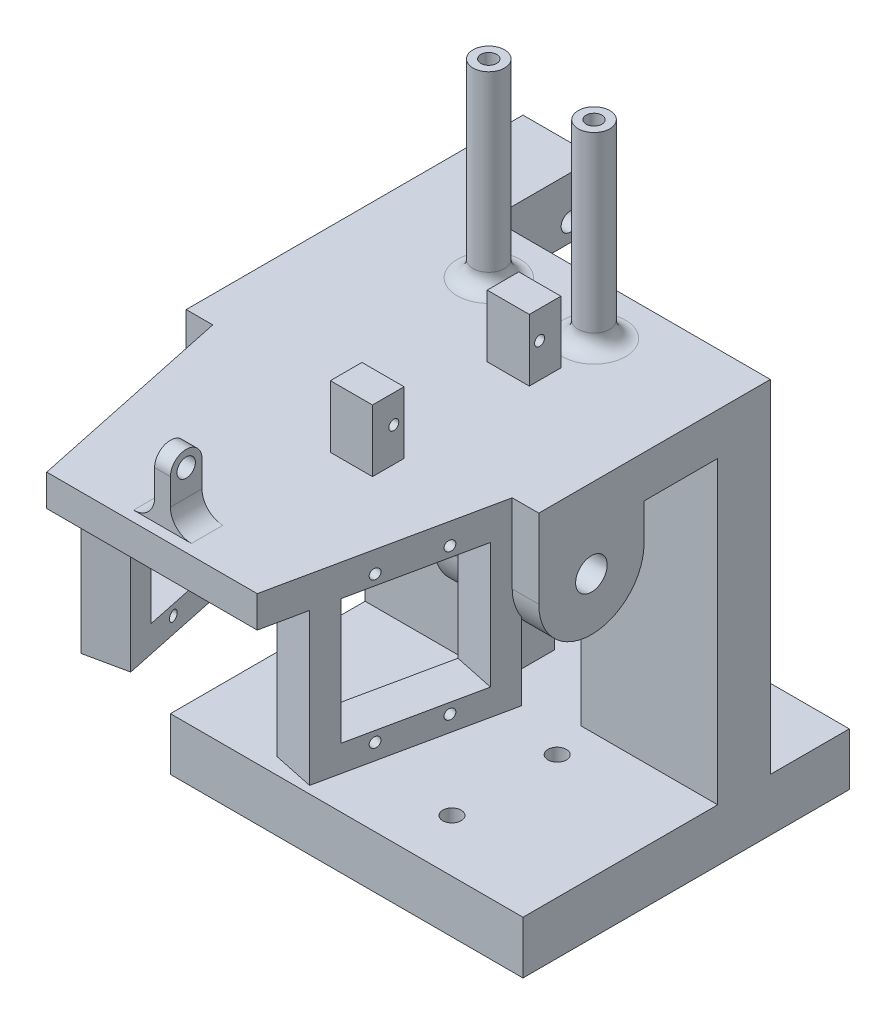
SolidWorks part; units mm, degrees
ref_plane "前视基准面" through (0, 0, 0) normal (0, 0, 1) x (1, 0, 0)
ref_plane "上视基准面" through (0, 0, 0) normal (0, 1, 0) x (1, 0, 0)
ref_plane "右视基准面" through (0, 0, 0) normal (1, 0, 0) x (0, 0, -1)
sketch "草图1" plane through (0, 0, 0) normal (0, 1, 0) x (1, 0, 0)
  line L1 (-33.5, 31) -> (33.5, 31)
  line L2 (-33.5, 31) -> (-33.5, -31)
  line L3 (-33.5, -31) -> (33.5, -31)
  line L4 (33.5, 31) -> (33.5, -31)
  line L5 (-33.5, 31) -> (33.5, -31) construction
  line L6 (-33.5, -31) -> (33.5, 31) construction
  point P0 (0, 0)
  dimension "D1" = 62
  dimension "D2" = 67
extrude "凸台-拉伸1" add sketch "草图1" along normal blind 10
sketch "草图3" plane through (0, 10, 0) normal (0, 1, 0) x (1, 0, 0)
  line L0 (-33.5, 31) -> (-33.5, -31) construction
  line L1 (-33.5, 36) -> (-19.5, 36)
  line L2 (-33.5, 36) -> (-33.5, 16)
  line L3 (-33.5, 16) -> (-19.5, 16)
  line L4 (-19.5, 36) -> (-19.5, 16)
  line L5 (33.5, 31) -> (-33.5, 31) construction
  dimension "D1" = 20
  dimension "D2" = 5
  dimension "D3" = 19.5
extrude "凸台-拉伸2" add sketch "草图3" along normal blind 12.5
sketch "草图4" plane through (-33.5, 0, 0) normal (-1, 0, 0) x (0, 0, 1)
  line L1 (-16, 10) -> (-6, 10)
  line L2 (-16, 10) -> (-16, 75)
  line L3 (-16, 75) -> (-6, 75)
  line L4 (-6, 10) -> (-6, 75)
  dimension "D1" = 10
  dimension "D2" = 65
extrude "凸台-拉伸3" add sketch "草图4" against normal blind 67
sketch "草图5" plane through (0, 75, 0) normal (0, 1, 0) x (1, 0, 0)
  line L0 (33.5, -31) -> (33.5, 6) construction
  line L1 (-33.5, 16) -> (33.5, 16)
  line L2 (-33.5, 16) -> (-33.5, -28)
  line L3 (-33.5, -28) -> (33.5, -28)
  line L4 (33.5, 16) -> (33.5, -28)
  dimension "D1" = 44
extrude "凸台-拉伸4" add sketch "草图5" against normal blind 8
sketch "草图6" plane through (33.5, 0, 0) normal (1, 0, 0) x (0, 0, -1)
  line L0 (6, 10) -> (6, 67) construction
  line L1 (-28, 75) -> (16, 75) construction
  line L2 (-28, 60) -> (-28, 67)
  line L3 (-28, 67) -> (6, 67) construction
  line L5 (-28, 67) -> (-8, 67)
  line L6 (-8, 67) -> (-8, 60)
  arc A0 (-28, 60) -> (-8, 60) centre (-18, 60) ccw
  dimension "D1" = 24
  dimension "D2" = 15
  dimension "D3" = 20
extrude "凸台-拉伸5" add sketch "草图6" against normal blind 20
sketch "草图7" plane through (33.5, 0, 0) normal (1, 0, 0) x (0, 0, -1)
  line L0 (-28, 60) -> (-28, 70.0002)
  line L1 (-28, 60) -> (-28, 75) construction
  line L2 (-28, 70.0002) -> (-8, 70.0002)
  line L3 (-8, 70.0002) -> (-8, 60)
  arc A0 (-28, 60) -> (-8, 60) centre (-18, 60) ccw construction
  arc A1 (-28, 60) -> (-8, 60) centre (-18, 60) ccw
extrude "切除-拉伸1" cut sketch "草图7" against normal blind 8 from offset 6 offset against normal yes
sketch "草图8" plane through (0, 75, 0) normal (0, 1, 0) x (1, 0, 0)
  line L0 (0, -68) -> (20, -68)
  line L2 (20, -68) -> (28.4525, -28)
  line L3 (28.4525, -28) -> (0, -28)
  line L4 (0, -28) -> (0, -68)
  line L5 (-33.5, -28) -> (33.5, -28) construction
  dimension "D1" = 20
  dimension "D2" = 40
extrude "凸台-拉伸6" add sketch "草图8" against normal blind 6
sketch "草图9" plane through (33.5, 0, 0) normal (1, 0, 0) x (0, 0, -1)
  circle A0 centre (-18, 60) radius 3
  dimension "D1" = 6
extrude "切除-拉伸2" cut sketch "草图9" against normal blind 23
sketch "草图10" plane through (32.9001, 0, 6.9522) normal (0.9784, 0, 0.2067) x (0.2067, 0, -0.9784)
  line L1 (-49, 75) -> (-20, 75)
  line L4 (-20, 75) -> (-20, 40.2)
  line L5 (-20, 40.2) -> (-48, 40.2)
  line L9 (-49, 45.2) -> (-25, 45.2)
  line L10 (-25, 45.2) -> (-25, 69)
  line L11 (-25, 69) -> (-49, 69)
  line L12 (-62.3959, 75) -> (-21.5126, 75) construction
  line L14 (-49, 75) -> (-54, 75)
  line L15 (-62.3959, 75) -> (-21.5126, 75) construction
  line L16 (-49, 69) -> (-49, 45.2)
  line L17 (-48, 40.2) -> (-54, 40.2)
  line L18 (-54, 75) -> (-54, 40.2)
  dimension "D1" = 5
  dimension "D2" = 5
  dimension "D3" = 29
  dimension "D4" = 20
  dimension "D5" = 24
  dimension "D6" = 28
  dimension "D7" = 5
  dimension "D8" = 6
  dimension "D9" = 23.8
extrude "凸台-拉伸7" add sketch "草图10" against normal blind 8
sketch "草图12" plane through (0, 75, 0) normal (0, 1, 0) x (1, 0, 0)
  line L1 (-33.5, 36) -> (-19.5, 36)
  line L2 (-33.5, 36) -> (-33.5, 16)
  line L3 (-33.5, 16) -> (-19.5, 16)
  line L4 (-19.5, 36) -> (-19.5, 16)
extrude "凸台-拉伸8" add sketch "草图12" against normal blind 11.5
sketch "草图13" plane through (25.0729, 0, 5.2982) normal (-0.9784, 0, -0.2067) x (-0.2067, 0, 0.9784)
  line L0 (62.3959, 69) -> (54, 69) construction
  line L7 (25, 69) -> (25, 45.2) construction
  line L8 (25, 45.2) -> (49, 45.2) construction
  circle A0 centre (43.5, 70.95) radius 0.95
  circle A1 centre (31.5, 70.95) radius 0.95
  circle A2 centre (31.5, 43.25) radius 0.95
  circle A3 centre (43.5, 43.25) radius 0.95
  dimension "D2" = 6.5
  dimension "D3" = 1.95
  dimension "D4" = 1.95
  dimension "D5" = 12
  dimension "D6" = 1.9
  dimension "D7" = 1.9
  dimension "D13" = 1.9
  dimension "D14" = 1.9
extrude "切除-拉伸4" cut sketch "草图13" against normal up to surface (8 mm away) up to face at (24.7288, 60.3828, 45.6217)
sketch "草图14" plane through (0, 75, 0) normal (0, 1, 0) x (1, 0, 0)
  line L0 (33.5, 6) -> (-33.5, 6) construction
  line L1 (3.7, -2) -> (11.7, -2)
  line L2 (3.7, -2) -> (3.7, -8)
  line L3 (3.7, -8) -> (11.7, -8)
  line L4 (11.7, -2) -> (11.7, -8)
  line L5 (11.7, -31.8) -> (11.7, -37.8)
  line L6 (3.7, -37.8) -> (11.7, -37.8)
  line L7 (3.7, -31.8) -> (3.7, -37.8)
  line L8 (3.7, -31.8) -> (11.7, -31.8)
  dimension "D1" = 11.7
  dimension "D2" = 3.7
  dimension "D3" = 6
  dimension "D4" = 14
  dimension "D5" = 6
  dimension "D6" = 8
  dimension "D7" = 23.8
extrude "凸台-拉伸9" add sketch "草图14" along normal blind 11.8
sketch "草图15" plane through (3.7, 0, 0) normal (-1, 0, 0) x (0, 0, 1)
  line L0 (8, 86.8) -> (8, 75) construction
  line L1 (28, 75) -> (-36, 75) construction
  line L2 (31.8, 75) -> (37.8, 75) construction
  line L3 (31.8, 86.8) -> (31.8, 75) construction
  circle A0 centre (33.75, 81.5) radius 0.95
  circle A1 centre (6.05, 81.5) radius 0.95
  dimension "D1" = 1.95
  dimension "D2" = 1.95
  dimension "D3" = 1.9
  dimension "D4" = 1.9
  dimension "D5" = 6.5
  dimension "D6" = 6.5
extrude "切除-拉伸5" cut sketch "草图15" against normal blind 11.8
sketch "草图16" plane through (0, 75, 0) normal (0, 1, 0) x (1, 0, 0)
  line L1 (-1.5, -60) -> (1.5, -60)
  line L2 (-1.5, -60) -> (-1.5, -66)
  line L3 (-1.5, -66) -> (1.5, -66)
  line L4 (1.5, -60) -> (1.5, -66)
  point P4 (0, -66)
  dimension "D2" = 6
  dimension "D3" = 3
  dimension "D4" = 60
extrude "凸台-拉伸10" add sketch "草图16" along normal blind 12
fillet "圆角1" 2 edges at (0, 87, 66) (0, 87, 60) type full round first side face at (0, 79.8, 66) second side face at (0, 79.8, 60) middle face at (0, 87, 63)
sketch "草图17" plane through (-1.5, 0, 0) normal (-1, 0, 0) x (0, 0, 1)
  circle A0 centre (63, 84) radius 1.75
  arc A1 (66, 84) -> (60, 84) centre (63, 84) ccw construction
  dimension "D1" = 3.5
extrude "切除-拉伸6" cut sketch "草图17" against normal blind 7
sketch "草图18" plane through (0, 75, 0) normal (0, 1, 0) x (1, 0, 0)
  line L0 (33.5, 16) -> (-19.5, 16) construction
  circle A0 centre (10, 6) radius 3
  dimension "D1" = 6
  dimension "D2" = 10
  dimension "D3" = 10
extrude "凸台-拉伸11" add sketch "草图18" along normal blind 36
fillet "圆角2" radius 3 1 edges at (10, 75, -3)
mirror "镜向1" about plane through (0, 0, 0) normal (1, 0, 0) of "圆角2", "凸台-拉伸11", "切除-拉伸4", "凸台-拉伸7", "切除-拉伸2", "凸台-拉伸6", "切除-拉伸1", "凸台-拉伸5"
sketch "草图20" plane through (-33.5, 0, 0) normal (-1, 0, 0) x (0, 0, 1)
  line L0 (-36, 63.5) -> (-16, 63.5) construction
  line L1 (-36, 63.5) -> (-36, 75) construction
  circle A0 centre (-31, 67) radius 1.75
  circle A1 centre (-21, 67) radius 1.75
  circle A2 centre (-31, 19) radius 1.75
  circle A3 centre (-21, 19) radius 1.75
  dimension "D1" = 3.5
  dimension "D2" = 10
  dimension "D3" = 48
  dimension "D4" = 3.5
  dimension "D5" = 5
extrude "切除-拉伸7" cut sketch "草图20" against normal blind 35
sketch "草图21" plane through (0, 0, -16) normal (0, 0, -1) x (-1, 0, 0)
  line L1 (-7.5, 65) -> (7.5, 65)
  line L2 (-7.5, 65) -> (-7.5, 10)
  line L3 (-7.5, 10) -> (7.5, 10)
  line L4 (7.5, 65) -> (7.5, 10)
  line L5 (-33.5, 10) -> (19.5, 10) construction
  point P8 (0, 10)
  dimension "D1" = 15
  dimension "D2" = 55
extrude "切除-拉伸8" cut sketch "草图21" against normal blind 35
sketch "草图24" plane through (0, 10, 0) normal (0, 1, 0) x (1, 0, 0)
  line L0 (-33.5, -31) -> (33.5, -31) construction
  circle A0 centre (-10, -21) radius 1.75
  circle A1 centre (10, -21) radius 1.75
  circle A2 centre (-10, -1) radius 1.75
  circle A3 centre (10, -1) radius 1.75
  point P10 (0, -31)
  dimension "D1" = 20
  dimension "D2" = 20
  dimension "D5" = 10
  dimension "D6" = 3.5
  dimension "D7" = 10
  dimension "D3" = 20
  dimension "D4" = 20
extrude "切除-拉伸11" cut sketch "草图24" against normal blind 18
sketch "草图25" plane through (0, 111, 0) normal (0, 1, 0) x (1, 0, 0)
  circle A0 centre (10, 6) radius 1.5
  circle A1 centre (-10, 6) radius 1.5
  dimension "D1" = 3
  dimension "D2" = 3
extrude "切除-拉伸12" cut sketch "草图25" against normal blind 10
fillet "圆角3" radius 4 2 edges at (-1.5, 75, 63) (1.5, 75, 63)
sketch "草图26" plane through (0, 69, 0) normal (0, -1, 0) x (1, 0, 0)
  line L0 (-20, 68) -> (20, 68) construction
  line L1 (-5, 63.9) -> (5, 63.9)
  line L2 (-5, 63.9) -> (-5, 60.3)
  line L3 (-5, 60.3) -> (5, 60.3)
  line L4 (5, 63.9) -> (5, 60.3)
  line L5 (-5, 63.9) -> (5, 60.3) construction
  line L6 (-5, 60.3) -> (5, 63.9) construction
  line L7 (-33.5, -31) -> (-33.5, 31) construction
  point P0 (0, 62.1)
  dimension "D1" = 3.6
  dimension "D2" = 10
  dimension "D3" = 4.1
  dimension "D4" = 28.5
extrude "凸台-拉伸12" add sketch "草图26" along normal blind 1
sketch "草图27" plane through (0, 68, 0) normal (0, -1, 0) x (1, 0, 0)
  line L0 (-20, 68) -> (20, 68) construction
  line L1 (-33.5, -31) -> (-33.5, 31) construction
  circle A0 centre (0, 62) radius 1.4
  point P6 (-43.4255, 30.3841)
  dimension "D1" = 2.8
  dimension "D2" = 6
  dimension "D3" = 33.5
extrude "切除-拉伸13" cut sketch "草图27" against normal blind 4
